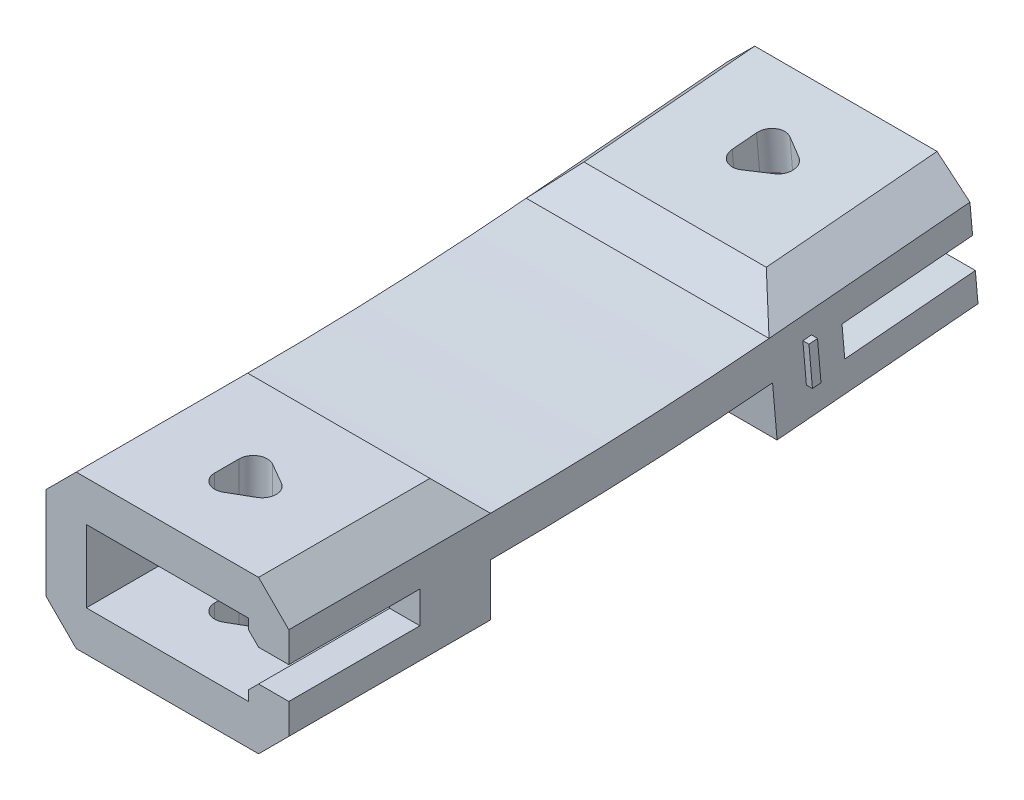
SolidWorks part; units mm, degrees
ref_plane "Front Plane" through (0, 0, 0) normal (0, 0, 1) x (1, 0, 0)
ref_plane "Top Plane" through (0, 0, 0) normal (0, 1, 0) x (1, 0, 0)
ref_plane "Right Plane" through (0, 0, 0) normal (1, 0, 0) x (0, 0, -1)
other "Configuration Table"
sketch "Sketch1" plane through (0, 0, 0) normal (0, 0, 1) x (1, 0, 0)
  line L1 (4.02, -1.79) -> (-4.02, -1.79)
  line L2 (4.02, -1.79) -> (4.02, 1.79)
  line L3 (4.02, 1.79) -> (-4.02, 1.79)
  line L4 (-4.02, -1.79) -> (-4.02, 1.79)
  line L5 (0, 1.79) -> (0, -1.79) construction
  line L6 (4.02, 0) -> (-4.02, 0) construction
  line L7 (-6.02, 3.79) -> (6.02, 3.79)
  line L8 (-6.02, 3.79) -> (-6.02, -3.79)
  line L9 (-6.02, -3.79) -> (6.02, -3.79)
  line L10 (6.02, 3.79) -> (6.02, -3.79)
  line L11 (0, -3.79) -> (0, 3.79) construction
  line L12 (-6.02, 0) -> (6.02, 0) construction
  point P0 (0, 0)
  point P4 (0, 0)
  dimension "D1" = 3.58
  dimension "D2" = 8.04
  dimension "D3" = 2
  dimension "D4" = 2
extrude "Boss-Extrude1" add sketch "Sketch1" along normal blind 8
extrude "Boss-Extrude2" add sketch "Sketch1<2>" against normal blind 2 contours L4 L1 L2 L3 | L10 L7 L8 L9 L1 L4 L3 L2 region at (0, 0, 0) region at (0, 3.6477, 0)
sketch "Sketch1<2>" plane through (0, 0, 0) normal (0, 0, 1) x (1, 0, 0) same geometry as "Sketch1"
sketch "Sketch3" plane through (6.02, 9.81, 0) normal (1, 0, 0) x (0, -1, 0)
  line L0 (13.6, 2) -> (9.52, 2)
  line L2 (8.9093, 15.9867) -> (12.9738, 16.3423)
  line L3 (13.6, -8) -> (13.6, 2) construction
  arc A1 (9.52, 2) -> (8.9093, 15.9867) centre (-150.9591, 2) ccw
  arc A3 (12.9738, 16.3423) -> (13.6, 2) centre (-150.9591, 2) cw construction
  dimension "D1" = 4.08
  dimension "D4" = 5
  dimension "D2" = 14
extrude "Extrude-Thin1" add sketch "Sketch3" along normal up to surface (-12.04 mm away) thin contours L0 A1 L2 up to face at (-6.02, 0, 3) thin type one direction reverse wall 2
sketch "Sketch5" plane through (0, -2.3561, -16.2716) normal (0, 0.0872, -0.9962) x (-1, 0, 0)
  line L1 (4.02, 1.1892) -> (-4.02, 1.1892)
  line L2 (4.02, 1.1892) -> (4.02, 4.7692)
  line L3 (4.02, 4.7692) -> (-4.02, 4.7692)
  line L4 (-4.02, 1.1892) -> (-4.02, 4.7692)
  line L5 (0, 4.7692) -> (0, 1.1892) construction
  line L6 (4.02, 2.9792) -> (-4.02, 2.9792) construction
  line L7 (-6.02, 6.7692) -> (6.02, 6.7692)
  line L8 (-6.02, 6.7692) -> (-6.02, -0.8108)
  line L9 (-6.02, -0.8108) -> (6.02, -0.8108)
  line L10 (6.02, 6.7692) -> (6.02, -0.8108)
  line L11 (0, -0.8108) -> (0, 6.7692) construction
  line L12 (-6.02, 2.9792) -> (6.02, 2.9792) construction
  line L13 (6.02, -0.8108) -> (-6.02, -0.8108) construction
  point P0 (0, 2.9792)
  point P4 (0, 2.9792)
  line M23 (6.02, -0.8108) -> (-6.02, -0.8108)
  line M29 (-6.02, 3.2692) -> (6.02, 3.2692)
  dimension "D1" = 3.58
  dimension "D2" = 8.04
  dimension "D3" = 2
  dimension "D4" = 2
extrude "Boss-Extrude4" add sketch "Sketch5" along normal blind 10 contours M29 M23 | L7 L10 L2 L3 L4 L8 M29 region at (0, -1.6457, -16.2095) region at (0, 3.0434, -15.7992)
extrude "Boss-Extrude5" add sketch "Sketch5<4>" along normal blind 2 contours L8 L7 L10 L9
sketch "Sketch5<4>" plane through (0, -2.3561, -16.2716) normal (0, 0.0872, -0.9962) x (-1, 0, 0) same geometry as "Sketch5"
chamfer "Chamfer1" distance 1.5 angle 45 12 edges at (-6.02, 4.8231, -20.6626) (6.02, 4.8231, -20.6626) (6.02, 3.79, 3) (6.02, -3.79, 3) (-6.02, -3.79, 3) (-6.02, 3.79, 3) (0, 3.79, -2) (0, -3.1638, -16.3423) (6.02, -2.728, -21.3232) (-6.02, -2.728, -21.3232) (0, -3.79, -2) (0, 4.3874, -15.6816)
sketch "Sketch6" plane through (0, 3.79, 0) normal (0, 1, 0) x (1, 0, 0)
  line L0 (0, 2) -> (0, -8) construction
  line L4 (1.05, -3.3938) -> (0, -2.7876)
  line L5 (-1.05, -3.3938) -> (-1.05, -4.6062)
  line L6 (0, -5.2124) -> (1.05, -4.6062)
  line L7 (-6.02, 2) -> (6.02, 2) construction
  line L8 (4.52, -8) -> (-4.52, -8) construction
  line L9 (4.02, 0) -> (-4.02, 0) construction
  circle A0 centre (0, -4) radius 1.05 construction
  arc A1 (-1.05, -4.6062) -> (0, -5.2124) centre (-0.35, -4.6062) ccw
  arc A2 (0, -2.7876) -> (-1.05, -3.3938) centre (-0.35, -3.3938) ccw
  arc A3 (1.05, -3.3938) -> (1.05, -4.6062) centre (0.7, -4) cw
  point P15 (-1.05, -5.8187)
  point P18 (-1.05, -2.1813)
  dimension "D3" = 0.7
  dimension "D1" = 2.1
  dimension "D2" = 4
sketch "Sketch7" plane through (0, 2.9925, 0.2618) normal (0, 0.9962, 0.0872) x (1, 0, 0)
  line L0 (0, 26.0043) -> (0, 16.0043) construction
  line L4 (1.05, 22.6106) -> (0, 23.2168)
  line L5 (-1.05, 22.6106) -> (-1.05, 21.3981)
  line L6 (0, 20.7919) -> (1.05, 21.3981)
  line L7 (6.02, 16.0043) -> (-6.02, 16.0043) construction
  line L8 (4.52, 26.0043) -> (-4.52, 26.0043) construction
  line L9 (-4.02, 18.0043) -> (4.02, 18.0043) construction
  circle A0 centre (0, 22.0043) radius 1.05 construction
  arc A1 (-1.05, 21.3981) -> (0, 20.7919) centre (-0.35, 21.3981) ccw
  arc A2 (1.05, 22.6106) -> (1.05, 21.3981) centre (0.7, 22.0043) cw
  arc A3 (0, 23.2168) -> (-1.05, 22.6106) centre (-0.35, 22.6106) ccw
  dimension "D1" = 2.1
  dimension "D3" = 0.7
  dimension "D2" = 4
extrude "Cut-Extrude1" cut sketch "Sketch6" against normal through all both and the other way through all
extrude "Cut-Extrude2" cut sketch "Sketch7" against normal through all both and the other way through all
sketch "Sketch8" plane through (0, 2.2664, -25.9054) normal (0, 0.0872, -0.9962) x (-1, 0, 0)
  line L1 (-8.02, 0.0039) -> (-4.02, 0.0039)
  line L2 (-8.02, 0.0039) -> (-8.02, -1.5761)
  line L3 (-8.02, -1.5761) -> (-4.02, -1.5761)
  line L4 (-4.02, 0.0039) -> (-4.02, -1.5761)
  line L5 (-6.02, -1.5761) -> (-6.02, 0.0039) construction
  line L6 (-8.02, -0.7861) -> (-4.02, -0.7861) construction
  line L8 (-6.02, -3.0761) -> (-6.02, 1.5039) construction
  line L9 (-4.02, -2.5761) -> (-4.02, 1.0039) construction
  line L10 (4.02, -2.5761) -> (-4.02, -2.5761) construction
  point P0 (-6.02, -0.7861)
  dimension "D1" = 1.58
  dimension "D2" = 4
  dimension "D3" = 1
extrude "Cut-Extrude3" cut sketch "Sketch8" against normal offset from surface (6.5 mm away) 1.5 up to face at (0, 0.7861, -18.0043)
sketch "Sketch9" plane through (0, 0, 8) normal (0, 0, 1) x (1, 0, 0)
  line L1 (8.02, 0.79) -> (4.02, 0.79)
  line L2 (8.02, 0.79) -> (8.02, -0.79)
  line L3 (8.02, -0.79) -> (4.02, -0.79)
  line L4 (4.02, 0.79) -> (4.02, -0.79)
  line L5 (6.02, -0.79) -> (6.02, 0.79) construction
  line L6 (8.02, 0) -> (4.02, 0) construction
  line L8 (6.02, -2.29) -> (6.02, 2.29) construction
  line L9 (4.02, -1.79) -> (4.02, 1.79) construction
  line L10 (-4.02, -1.79) -> (4.02, -1.79) construction
  point P0 (6.02, 0)
  dimension "D1" = 1.58
  dimension "D2" = 4
  dimension "D3" = 1
extrude "Cut-Extrude4" cut sketch "Sketch9" against normal offset from surface (6.5 mm away) 1.5 up to face at (0, 0, 0)
chamfer "Chamfer2" distance 0.5 angle 45 6 edges at (4.02, 1.9871, -22.6674) (4.02, 0.9168, -19.4986) (4.02, 0.4131, -22.8051) (4.02, 0.79, 4.75) (4.02, 0, 1.5) (4.02, -0.79, 4.75)
sketch "Sketch10" [suppressed] plane through (6.02, 0, 0) normal (1, 0, 0) x (0, 0, -1)
  line L0 (22.5646, 0.2607) -> (19.0779, -0.0444) construction
  line L2 (18.9838, 1.0315) -> (19.2087, -1.5387) construction
  line L3 (22.5646, 0.2607) -> (22.4269, 1.8347) construction
  line L4 (29.0399, 0.8272) -> (22.5646, 0.2607) construction
  text T0 "<b>III</b>" font "@Microsoft YaHei" height 2
extrude "Boss-Extrude6" [suppressed] add sketch "Sketch10" along normal blind 0.3
sketch "Sketch11" [suppressed] plane through (6.02, 0, 0) normal (1, 0, 0) x (0, 0, -1)
  line L0 (21.5656, 0.2171) -> (18.0789, -0.088) construction
  line L1 (17.9848, 0.9879) -> (18.2096, -1.5823) construction
  line L2 (28.0408, 0.7836) -> (21.5656, 0.2171) construction
  text T0 "<b>II</b>\r\n" font "@Microsoft YaHei" height 2
extrude "Boss-Extrude7" [suppressed] add sketch "Sketch11" along normal blind 0.3
sketch "Sketch12" plane through (6.02, 0, 0) normal (1, 0, 0) x (0, 0, -1)
  line L0 (19.5675, 0.1298) -> (16.0808, -0.1752) construction
  line L1 (15.9867, 0.9007) -> (16.2115, -1.6695) construction
  line L2 (26.0428, 0.6963) -> (19.5675, 0.1298) construction
  text T0 "<b>I</b>\r\n" font "@Microsoft YaHei" height 2
extrude "Boss-Extrude8" add sketch "Sketch12" along normal blind 0.3
equation "\"LF\" = 0.04mm"
equation "\"TF\" = 0.02mm"
equation "\"AngLF\"= 0.5"
equation "\"AngTF\"= 0.3"
equation "\"D2@Sketch1\"=8+2*\"TF\""
equation "\"D1@Sketch1\"=3.5+2*\"LF\""
